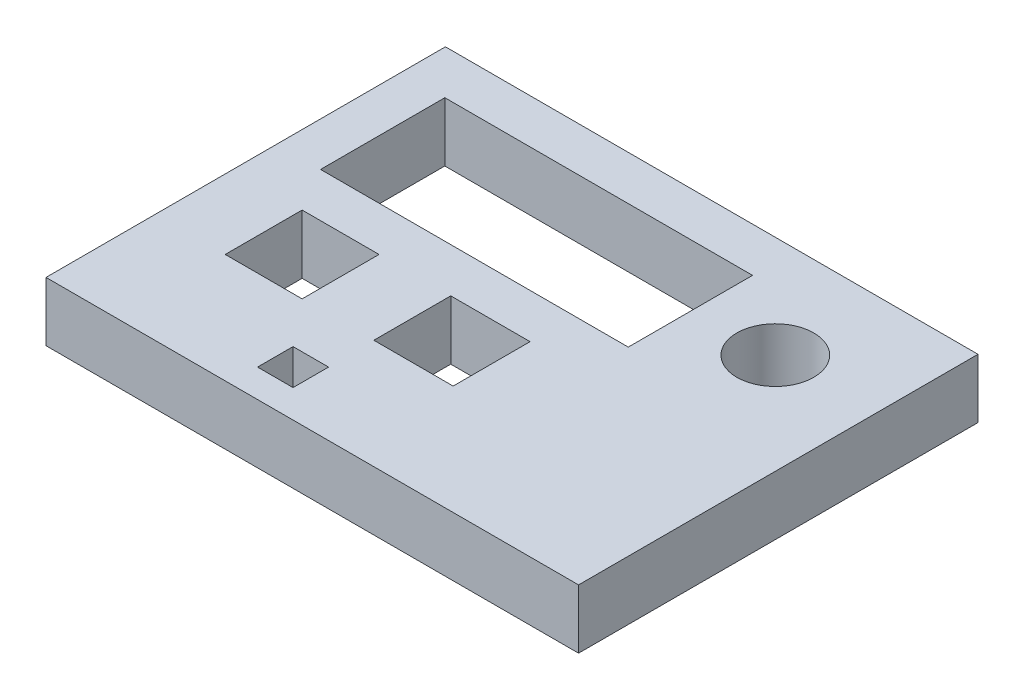
SolidWorks part; units mm, degrees
ref_plane "Front Plane" through (0, 0, 0) normal (0, 0, 1) x (1, 0, 0)
ref_plane "Top Plane" through (0, 0, 0) normal (0, 1, 0) x (1, 0, 0)
ref_plane "Right Plane" through (0, 0, 0) normal (1, 0, 0) x (0, 0, -1)
sketch "Sketch1" plane through (0, 0, 0) normal (0, 1, 0) x (1, 0, 0)
  line L0 (-8.1, -15.25) -> (5.3066, -15.25)
  line L1 (-45, -33.75) -> (45, -33.75)
  line L2 (-45, -33.75) -> (-45, 33.75)
  line L3 (-45, 33.75) -> (45, 33.75)
  line L4 (45, -33.75) -> (45, 33.75)
  line L5 (-45, -33.75) -> (45, 33.75) construction
  line L6 (-45, 33.75) -> (45, -33.75) construction
  line L7 (-8.1, -15.25) -> (-8.1, -2.25)
  line L8 (-8.1, -2.25) -> (5.3066, -2.25)
  line L9 (-37.6, 26.25) -> (14.4, 26.25)
  line L10 (-37.6, 26.25) -> (-37.6, 5.25)
  line L11 (-37.6, 5.25) -> (14.4, 5.25)
  line L12 (14.4, 26.25) -> (14.4, 5.25)
  line L13 (-33.217, -15.25) -> (-20.217, -15.25)
  line L14 (-33.217, -15.25) -> (-33.217, -2.25)
  line L15 (-33.217, -2.25) -> (-20.217, -2.25)
  line L16 (-20.217, -15.25) -> (-20.217, -2.25)
  line L21 (-45, -33.75) -> (-11, -33.75)
  line L22 (5.3066, -15.25) -> (5.3066, -2.25)
  line L23 (-11, -33.75) -> (-45, -33.75)
  line L24 (-11, -29) -> (-14, -29)
  line L25 (-14, -29) -> (-14, -23)
  line L26 (-14, -23) -> (-8, -23)
  line L27 (-8, -23) -> (-8, -29)
  line L28 (-8, -29) -> (-11, -29)
  circle A0 centre (28, 16.5) radius 6.5
  point P0 (0, 0)
  point P13 (0, 0)
  point P27 (0, 0)
  dimension "D7" = 13
  dimension "D1" = 90
  dimension "D2" = 67.5
  dimension "D3" = 7.5
  dimension "D4" = 13
  dimension "D5" = 52
  dimension "D6" = 21
  dimension "D8" = 13
  dimension "D9" = 7.5
  dimension "D10" = 17.25
  dimension "D11" = 29.5
  dimension "D12" = 7.75
  dimension "D13" = 7.5
  dimension "D14" = 3
  dimension "D15" = 3
  dimension "D16" = 6
  dimension "D17" = 13
extrude "Boss-Extrude1" add sketch "Sketch1" along normal blind 10 contours L1 L4 L3 L2 A0 L16 L13 L14 L15 L9 L12 L11 L10 L22 L7 L27 L28 L24 L25 L26 region at (-43.875, 0, 0)
